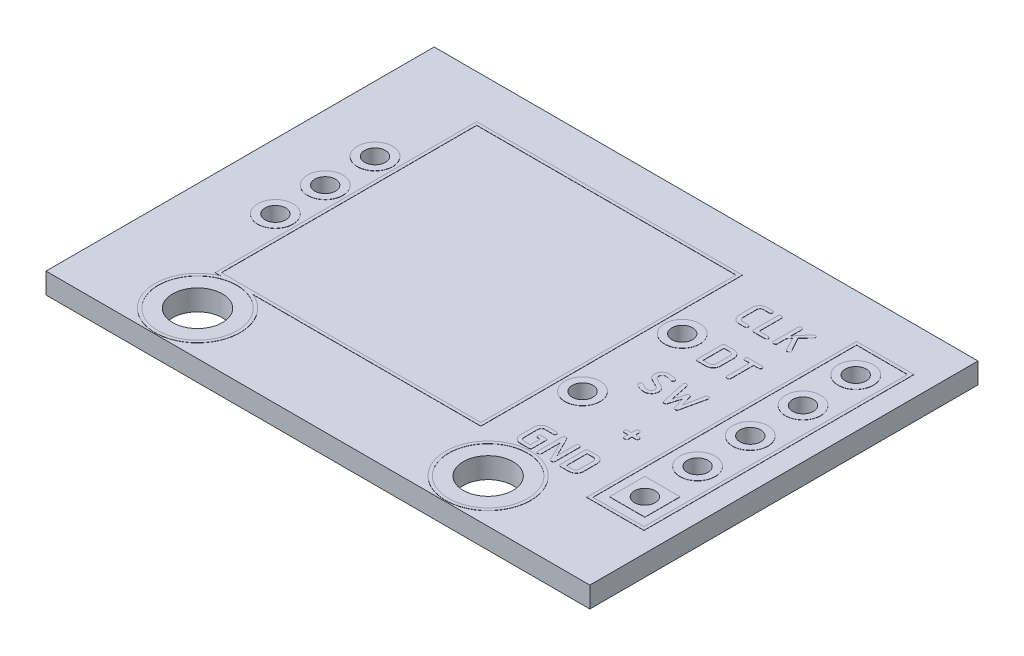
SolidWorks part; units mm, degrees
ref_plane "Front" through (0, 0, 0) normal (0, 0, 1) x (1, 0, 0)
ref_plane "Top" through (0, 0, 0) normal (0, 1, 0) x (1, 0, 0)
ref_plane "Right" through (0, 0, 0) normal (1, 0, 0) x (0, 0, -1)
sketch "草图1" plane through (0, 0, 0) normal (0, 1, 0) x (1, 0, 0)
  line L1 (0, 0) -> (26.2, 0)
  line L2 (0, 0) -> (0, 18.7)
  line L3 (0, 18.7) -> (26.2, 18.7)
  line L4 (26.2, 0) -> (26.2, 18.7)
  circle A0 centre (19.2, 2.1) radius 1.2
  circle A1 centre (5.2, 2.1) radius 1.2
  circle A2 centre (23.85, 5) radius 0.5
  circle A3 centre (23.85, 7.54) radius 0.5
  circle A4 centre (23.85, 10.08) radius 0.5
  circle A5 centre (23.85, 12.62) radius 0.5
  circle A6 centre (23.85, 15.16) radius 0.5
  dimension "D3" = 2.4
  dimension "D4" = 2.4
  dimension "D9" = 1
  dimension "D12" = 5
  dimension "D1" = 26.2
  dimension "D2" = 18.7
  dimension "D5" = 7
  dimension "D6" = 14
  dimension "D7" = 5.2
  dimension "D8" = 16.6
  dimension "D10" = 2.35
  dimension "D11" = 5
extrude "凸台-拉伸1" add sketch "草图1" along normal blind 0.5 and the other way blind 0.5
sketch "草图2" plane through (0, -0.5, 0) normal (0, -1, 0) x (1, 0, 0)
  line L0 (3.15, -7.5) -> (3.15, -13.705) construction
  line L1 (3.25, -7.5) -> (3.05, -7.5) construction
  line L2 (3.05, -7.9) -> (3.8248, -7.9) construction
  line L3 (3.05, -8.3) -> (3.05, -7.5) construction
  line L4 (3.15, -7.9) -> (17.95, -7.9) construction
  line L5 (3.15, -7.9) -> (3.15, -10.3) construction
  circle A0 centre (3.15, -7.9) radius 0.4994
  circle A1 centre (17.95, -7.9) radius 0.4994
  circle A3 centre (17.95, -12.7) radius 0.4994
  circle A4 centre (3.15, -10.3) radius 0.4994
  circle A5 centre (3.15, -12.7) radius 0.4994
  circle A42 centre (17.95, -10.3) radius 0.4994 [skipped]
  dimension "D1" = 0.9989
  dimension "D2" = 2
  dimension "D4" = 14.8
  dimension "D5" = 2.4
  dimension "D3" = 3
extrude "切除-拉伸1" cut sketch "草图2" against normal blind 2
sketch "草图6" plane through (0, 0.5, 0) normal (0, 1, 0) x (1, 0, 0)
  line L1 (24.6991, 4.15) -> (23.0009, 4.15)
  line L2 (24.6991, 4.15) -> (24.6991, 5.85)
  line L3 (24.6991, 5.85) -> (23.0009, 5.85)
  line L4 (23.0009, 4.15) -> (23.0009, 5.85)
  line L5 (24.6991, 4.15) -> (23.0009, 5.85) construction
  line L6 (24.6991, 5.85) -> (23.0009, 4.15) construction
  circle A0 centre (23.85, 15.16) radius 0.85
  circle A1 centre (23.85, 15.16) radius 0.5
  circle A2 centre (23.85, 15.16) radius 0.5
  circle A3 centre (23.85, 12.62) radius 0.5
  circle A4 centre (23.85, 12.62) radius 0.5
  circle A5 centre (23.85, 10.08) radius 0.5
  circle A6 centre (23.85, 10.08) radius 0.5
  circle A7 centre (23.85, 7.54) radius 0.5
  circle A8 centre (23.85, 7.54) radius 0.5
  circle A9 centre (23.85, 5) radius 0.5
  circle A10 centre (23.85, 5) radius 0.5
  circle A11 centre (23.85, 12.62) radius 0.85
  circle A13 centre (23.85, 10.08) radius 0.85
  circle A15 centre (3.15, 7.9) radius 0.4994
  circle A16 centre (3.15, 7.9) radius 0.4994
  circle A17 centre (17.95, 7.9) radius 0.4994
  circle A18 centre (17.95, 7.9) radius 0.4994
  circle A19 centre (17.95, 12.7) radius 0.4994
  circle A20 centre (17.95, 12.7) radius 0.4994
  circle A21 centre (3.15, 10.3) radius 0.4994
  circle A22 centre (3.15, 10.3) radius 0.4994
  circle A23 centre (3.15, 12.7) radius 0.4994
  circle A24 centre (3.15, 12.7) radius 0.4994
  circle A25 centre (23.85, 7.54) radius 0.85
  circle A26 centre (23.85, 5) radius 0.85 construction
  circle A27 centre (3.15, 7.9) radius 0.8494
  circle A28 centre (17.95, 7.9) radius 0.8494
  circle A29 centre (17.95, 12.7) radius 0.8494
  circle A30 centre (3.15, 10.3) radius 0.8494
  circle A31 centre (3.15, 12.7) radius 0.8494
  dimension "D1" = 0
  dimension "D2" = 0
  dimension "D3" = 0
  dimension "D4" = 0
  dimension "D5" = 0
  dimension "D6" = 0.35
  dimension "D8" = 0
  dimension "D9" = 0
  dimension "D10" = 0
  dimension "D11" = 0
  dimension "D12" = 0
extrude "凸台-拉伸4" add sketch "草图6" along normal blind 0.01
mirror "镜向1" about plane through (0, 0, 0) normal (0, 1, 0) of "凸台-拉伸4"
sketch "草图3" plane through (0, 0.5, 0) normal (0, 1, 0) x (1, 0, 0)
  line L1 (16.8, 16.45) -> (4.3, 16.45)
  line L2 (16.8, 16.45) -> (16.8, 4.15)
  line L3 (16.8, 4.15) -> (4.3, 4.15)
  line L4 (4.3, 16.45) -> (4.3, 4.15)
  line L5 (16.8, 16.45) -> (4.3, 4.15) construction
  line L6 (16.8, 4.15) -> (4.3, 16.45) construction
  line L7 (4.55, 10.3) -> (4.55, 5.66) construction
  line L8 (24.77, 16.43) -> (22.97, 16.43) construction
  line L9 (25.08, 3.73) -> (22.62, 3.73)
  line L10 (25.08, 3.73) -> (25.08, 16.43)
  line L11 (25.08, 16.43) -> (22.62, 16.43)
  line L12 (22.62, 3.73) -> (22.62, 16.43)
  line L13 (25.08, 3.73) -> (22.62, 16.43) construction
  line L14 (25.08, 16.43) -> (22.62, 3.73) construction
  line L15 (22.62, 15.96) -> (22.62, 14.36) construction
  line L16 (16.95, 16.6) -> (4.15, 16.6)
  line L17 (4.15, 16.6) -> (4.15, 4)
  line L18 (16.95, 4) -> (5.9697, 4)
  line L19 (16.95, 16.6) -> (16.95, 4)
  line L20 (25.23, 16.58) -> (22.47, 16.58)
  line L21 (22.47, 3.58) -> (22.47, 16.58)
  line L22 (25.23, 3.58) -> (22.47, 3.58)
  line L23 (25.23, 3.58) -> (25.23, 16.58)
  line L24 (4.4303, 4) -> (4.15, 4)
  line L26 (16.95, 4) -> (4.15, 4) construction
  circle A0 centre (5.2, 2.1) radius 1.9
  circle A1 centre (19.2, 2.1) radius 1.9
  arc A2 (4.4303, 4) -> (5.9697, 4) centre (5.2, 2.1) ccw
  circle A3 centre (19.2, 2.1) radius 2.05
  circle A5 centre (5.2, 2.1) radius 2.05 construction
  point P9 (10.55, 10.3)
  point P17 (23.85, 10.08)
  point P37 (7.25, 2.1)
  dimension "D1" = 3.8
  dimension "D3" = 0.25
  dimension "D4" = 0.15
  dimension "D5" = 0.15
  dimension "D2" = 0.15
extrude "凸台-拉伸2" add sketch "草图3" along normal blind 0.01
sketch "草图4" plane through (0, 0.5, 0) normal (0, 1, 0) x (1, 0, 0)
  line L0 (21.4313, 14.4912) -> (-3.813, 14.4912) construction
  text T0 "CLK\r\nDT\r\nSW\r\n+\r\nGND" font "@Adobe Heiti Std R" height 1.35
extrude "凸台-拉伸3" add sketch "草图4" along normal blind 0.01
